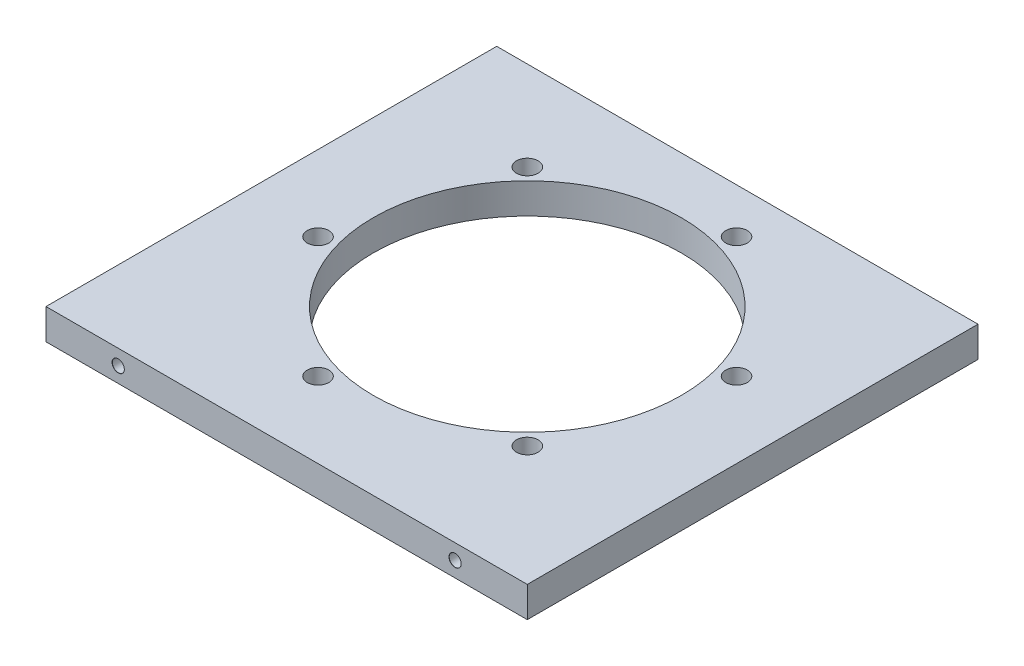
SolidWorks part; units mm, degrees
material "6061 Alloy"
ref_plane "Front Plane" through (0, 0, 0) normal (0, 0, 1) x (1, 0, 0)
ref_plane "Top Plane" through (0, 0, 0) normal (0, 1, 0) x (1, 0, 0)
ref_plane "Right Plane" through (0, 0, 0) normal (1, 0, 0) x (0, 0, -1)
sketch "Sketch1" plane through (0, 0, 0) normal (0, 1, 0) x (1, 0, 0)
  line L1 (-50, -50) -> (50, -50)
  line L2 (-50, -50) -> (-50, 50)
  line L3 (-50, 50) -> (50, 50)
  line L4 (50, -50) -> (50, 50)
  line L5 (-50, -50) -> (50, 50) construction
  line L6 (-50, 50) -> (50, -50) construction
  circle A1 centre (0, 0) radius 39.5
  arc A5 (-25.1023, 25.1023) -> (9.1881, 34.2904) centre (0, 0) cw
  arc A7 (9.1881, 34.2904) -> (-34.2904, -9.1881) centre (0, 0) ccw
  arc A9 (-34.2904, -9.1881) -> (-9.1881, -34.2904) centre (0, 0) ccw
  arc A11 (-9.1881, -34.2904) -> (25.1023, -25.1023) centre (0, 0) ccw
  circle A13 centre (0, 0) radius 32
  arc A14 (25.1023, -25.1023) -> (34.2904, 9.1881) centre (0, 0) ccw
extrude "Boss-Extrude3" add sketch "Sketch1" along normal blind 6.35 contours L1 L4 L3 L2 A1 | A1 A13 region at (-48.5858, 0, 0) region at (-38.3828, 0, 0)
hole_wizard "M4 Clearance Hole2" positions "Sketch6" profile "Sketch7" hole size "M4" standard "ANSI Metric" end condition through all
sketch "Sketch6" plane through (0, 0, 0) normal (0, -1, 0) x (-1, 0, 0)
  point P0 (-9.1881, 34.2904)
  point P3 (25.1023, 25.1023)
  point P6 (34.2904, -9.1881)
  point P9 (9.1881, -34.2904)
  point P12 (-25.1023, -25.1023)
  point P15 (-34.2904, 9.1881)
sketch "Sketch7" plane through (9.1881, 0, -34.2904) normal (1, 0, 0) x (0, 0, -1)
  line L0 (0, 0) -> (0, 6.35)
  line L1 (0, 6.35) -> (2.25, 6.35)
  line L2 (2.25, 6.35) -> (2.25, 0.025)
  line L3 (2.25, 0.025) -> (2.275, 0)
  line L5 (2.275, 0) -> (0, 0)
  line L6 (-2.25, 0.025) -> (-2.275, 0) construction
  line L11 (0, -6.35) -> (0, 107.95) construction
  dimension "Thru Hole Dia." = 4.5
  dimension "Thru Hole Depth" = 6.35
  dimension "Near C'Sink Dia." = 4.55
  dimension "Near C'Sink Angle" = 90
sketch "Sketch13" plane through (0, 6.35, 0) normal (0, 1, 0) x (1, 0, 0)
  line L0 (-50, -50) -> (-46.1091, -46.1091)
  line L1 (-46.1091, -46.1091) -> (-68.3017, -23.9166)
  line L2 (-46.1091, -46.1091) -> (-23.9166, -68.3017)
sketch "Sketch16" plane through (0, 6.35, 0) normal (0, 1, 0) x (1, 0, 0)
  line L0 (-50, -50) -> (-55, -50)
  line L1 (-50, -50) -> (50, -50) construction
  line L2 (-55, -50) -> (-55, -70)
  line L3 (-50, -50) -> (-75, -50)
  line L4 (-75, -50) -> (-75, -70)
  line L5 (-75, -70) -> (-55, -70)
  line L6 (-50, 50) -> (-55, 50)
  line L7 (-50, 50) -> (50, 50) construction
  line L8 (50, 50) -> (55, 50)
  line L9 (50, -50) -> (55, -50)
  line L11 (-55, 50) -> (-75, 50)
  line L12 (-55, 50) -> (-55, 70)
  line L13 (-55, 70) -> (-75, 70)
  line L14 (-75, 50) -> (-75, 70)
  line L15 (55, 50) -> (75, 50)
  line L16 (55, 50) -> (55, 70)
  line L17 (55, 70) -> (75, 70)
  line L18 (75, 50) -> (75, 70)
  line L19 (55, -50) -> (75, -50)
  line L20 (55, -50) -> (55, -70)
  line L21 (55, -70) -> (75, -70)
  line L22 (75, -50) -> (75, -70)
sketch "Sketch23" plane through (0, 6.35, 0) normal (0, 1, 0) x (1, 0, 0)
  line L0 (-50, -50) -> (-50, -55)
  line L1 (-50, -50) -> (-50, 50) construction
  line L2 (-50, 50) -> (-50, 55)
  line L3 (85, 50) -> (50, 55)
  line L4 (-50, 50) -> (50, 50) construction
  line L5 (50, -50) -> (50, 50) construction
  line L6 (50, -50) -> (50, -55)
  line L8 (-50, 55) -> (-70, 55)
  line L9 (-50, 55) -> (-50, 75)
  line L10 (-50, 75) -> (-70, 75)
  line L11 (-70, 55) -> (-70, 75)
  line L12 (50, 55) -> (70, 55)
  line L13 (50, 55) -> (50, 75)
  line L14 (50, 75) -> (70, 75)
  line L15 (70, 55) -> (70, 75)
  line L16 (50, -55) -> (70, -55)
  line L17 (50, -55) -> (50, -75)
  line L18 (50, -75) -> (70, -75)
  line L19 (70, -55) -> (70, -75)
  line L20 (-50, -55) -> (-70, -55)
  line L21 (-50, -55) -> (-50, -75)
  line L22 (-50, -75) -> (-70, -75)
  line L23 (-70, -55) -> (-70, -75)
sketch "Sketch24" plane through (0, 0, 50) normal (0, 0, 1) x (1, 0, 0)
  line L0 (-50, 3.175) -> (-35, 3.175)
  line L1 (-50, 6.35) -> (-50, 0) construction
  line L2 (50, 3.175) -> (35, 3.175)
  line L3 (50, 6.35) -> (50, 0) construction
hole_wizard "Tap Drill for M3x0.5 Tap2" positions "Sketch27" profile "Sketch28" hole size "M3x0.5" standard "ANSI Metric"
sketch "Sketch27" plane through (0, 0, 50) normal (0, 0, 1) x (1, 0, 0)
  point P0 (-35, 3.175)
  point P3 (35, 3.175)
sketch "Sketch28" plane through (-35, 3.175, 50) normal (1, 0, 0) x (0, -1, 0)
  line L0 (0, 0) -> (0, 10)
  line L1 (0, 10) -> (1.25, 9.2489)
  line L2 (1.25, 9.2489) -> (1.25, 0.025)
  line L3 (1.25, 0.025) -> (1.275, 0)
  line L5 (1.275, 0) -> (0, 0)
  line L6 (-1.25, 0.025) -> (-1.275, 0) construction
  line L10 (0, 10) -> (-1.25, 9.2489) construction
  line L11 (0, -6.35) -> (0, 107.95) construction
  dimension "Hole Dia." = 2.5
  dimension "Hole Depth" = 10
  dimension "Near C'Sink Dia." = 2.55
  dimension "Near C'Sink Angle" = 90
  dimension "Drill Angle" = 118
sketch "Sketch29" plane through (0, 0, -50) normal (0, 0, -1) x (-1, 0, 0)
  line L0 (-50, 3.175) -> (-35, 3.175)
  line L1 (50, 3.175) -> (35, 3.175)
sketch "Sketch32" plane through (0, 6.35, 0) normal (0, 1, 0) x (1, 0, 0)
  line L0 (50, -50) -> (50, 50) construction
  line L1 (-50, 50) -> (50, 50)
  line L2 (-50, 50) -> (-50, 43.65)
  line L3 (-50, 43.65) -> (50, 43.65)
  line L4 (50, 50) -> (50, 43.65)
extrude "Cut-Extrude1" cut sketch "Sketch32" against normal blind 10
sketch "Sketch33" plane through (0, 0, -43.65) normal (0, 0, -1) x (-1, 0, 0)
  line L0 (-50, 3.175) -> (-35, 3.175)
  line L1 (-50, 0) -> (-50, 6.35) construction
  line L2 (50, 3.175) -> (35, 3.175)
  line L3 (50, 0) -> (50, 6.35) construction
hole_wizard "Tap Drill for M3x0.5 Tap4" positions "Sketch34" profile "Sketch35" hole size "M3x0.5" standard "ANSI Metric"
sketch "Sketch34" plane through (0, 0, -43.65) normal (0, 0, -1) x (-1, 0, 0)
  point P0 (-35, 3.175)
  point P3 (35, 3.175)
sketch "Sketch35" plane through (35, 3.175, -43.65) normal (1, 0, 0) x (0, 1, 0)
  line L0 (0, 0) -> (0, 10)
  line L1 (0, 10) -> (1.25, 9.2489)
  line L2 (1.25, 9.2489) -> (1.25, 0.025)
  line L3 (1.25, 0.025) -> (1.275, 0)
  line L5 (1.275, 0) -> (0, 0)
  line L6 (-1.25, 0.025) -> (-1.275, 0) construction
  line L10 (0, 10) -> (-1.25, 9.2489) construction
  line L11 (0, -6.35) -> (0, 107.95) construction
  dimension "Hole Dia." = 2.5
  dimension "Hole Depth" = 10
  dimension "Near C'Sink Dia." = 2.55
  dimension "Near C'Sink Angle" = 90
  dimension "Drill Angle" = 118
